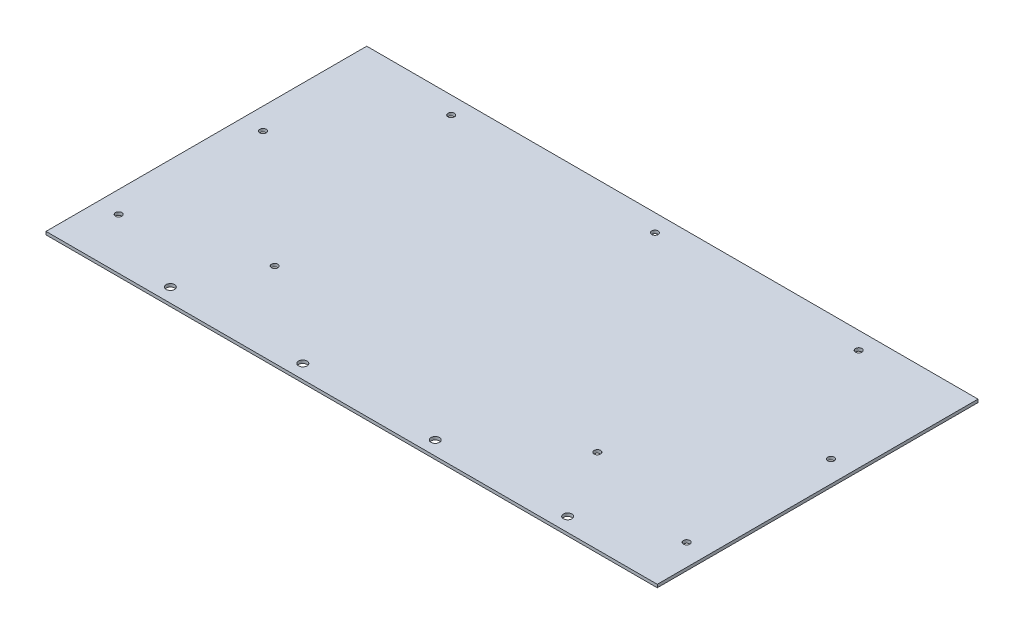
SolidWorks part; units mm, degrees
material "6061-T6 (SS)"
ref_plane "X-Y Datum" through (0, 0, 0) normal (0, 0, 1) x (1, 0, 0)
ref_plane "X-Z Datum" through (0, 0, 0) normal (0, 1, 0) x (1, 0, 0)
ref_plane "Y-Z Datum" through (0, 0, 0) normal (1, 0, 0) x (0, 0, -1)
sketch "Sketch1" plane through (0, 0, 0) normal (0, 0, 1) x (1, 0, 0)
  line L1 (-228.6115, -1.143) -> (228.6115, -1.143)
  line L2 (-228.6115, -1.143) -> (-228.6115, 1.143)
  line L3 (-228.6115, 1.143) -> (228.6115, 1.143)
  line L4 (228.6115, -1.143) -> (228.6115, 1.143)
  line L5 (-228.6115, -1.143) -> (228.6115, 1.143) construction
  line L6 (-228.6115, 1.143) -> (228.6115, -1.143) construction
  point P0 (0, 0)
  dimension "D1" = 2.286
  dimension "D2" = 457.223
extrude "Boss-Extrude1" add sketch "Sketch1" along normal blind 238.3152
sketch "Sketch2" plane through (0, 0, 0) normal (0, 0, -1) x (-1, 0, 0)
  line L22 (-228.6115, 1.143) -> (-228.6115, -1.143)
  line L23 (-228.6115, -1.143) -> (228.6115, -1.143)
  line L24 (228.6115, -1.143) -> (228.6115, 1.143)
  line L25 (228.6115, 1.143) -> (-228.6115, 1.143)
  line L26 (-228.6115, 1.143) -> (-228.6115, -1.143)
  line L27 (-228.6115, -1.143) -> (228.6115, -1.143)
  line L28 (228.6115, -1.143) -> (228.6115, 1.143)
  line L29 (228.6115, 1.143) -> (-228.6115, 1.143)
  dimension "D1" = 0
extrude "Boss-Extrude2" [suppressed] add sketch "Sketch2" along normal blind 3.175
sketch "Sketch9" plane through (0, 1.143, 0) normal (0, 1, 0) x (1, 0, 0)
  line L0 (-146.0615, -238.3152) -> (-146.0615, -229.4252) construction
  line L1 (228.6115, -238.3152) -> (-228.6115, -238.3152) construction
  line L2 (-228.6115, -238.3152) -> (-228.6115, 0) construction
  circle A0 centre (-146.0615, -229.4252) radius 3.175
  dimension "D2" = 82.55
  dimension "D3" = 6.35
  dimension "D1" = 8.89
extrude "Cut-Extrude10" cut sketch "Sketch9" against normal blind 2.54
pattern_linear "LPattern1" count 4 spacing 99.06 along (1, 0, 0) of "Cut-Extrude10"
sketch "Sketch10" plane through (0, -1.143, 0) normal (0, -1, 0) x (1, 0, 0)
  circle A0 centre (151.1185, 229.4252) radius 3.175 construction
  circle A1 centre (52.0585, 229.4252) radius 3.175 construction
  circle A2 centre (-47.0015, 229.4252) radius 3.175 construction
  circle A3 centre (-146.0615, 229.4252) radius 3.175 construction
  circle A4 centre (151.1185, 229.4252) radius 3.175
  circle A5 centre (52.0585, 229.4252) radius 3.175
  circle A6 centre (-47.0015, 229.4252) radius 3.175
  circle A7 centre (-146.0615, 229.4252) radius 3.175
sketch "Sketch15" plane through (0, 0, 238.3152) normal (0, 0, 1) x (1, 0, 0)
  line L4 (228.6115, -1.143) -> (228.6115, 1.143)
  line L5 (228.6115, 1.143) -> (-228.6115, 1.143)
  line L6 (-228.6115, 1.143) -> (-228.6115, -1.143)
  line L7 (-228.6115, -1.143) -> (228.6115, -1.143)
  line L8 (228.6115, -1.143) -> (228.6115, 1.143)
  line L9 (228.6115, 1.143) -> (-228.6115, 1.143)
  line L10 (-228.6115, 1.143) -> (-228.6115, -1.143)
  line L11 (-228.6115, -1.143) -> (228.6115, -1.143)
  dimension "D1" = 0
extrude "Boss-Extrude3" add sketch "Sketch15" along normal blind 1.5875
sketch "Sketch17" plane through (0, -1.143, 0) normal (0, -1, 0) x (1, 0, 0)
  point P0 (-212.419, 201.7248)
  point P1 (-212.419, 93.7748)
  point P3 (-152.4, 13.0175)
  point P5 (0, 13.0175)
  point P7 (152.4, 13.0175)
  point P9 (212.419, 93.7748)
  point P11 (212.419, 201.7248)
  point P13 (120.65, 176.776)
  point P15 (-120.65, 176.776)
hole_wizard "M4 Clearance Hole1" positions "Sketch17" profile "Sketch18" hole size "M4" standard "ANSI Metric" end condition through all
sketch "Sketch18" plane through (-212.419, -1.143, 201.7248) normal (1, 0, 0) x (0, 0, -1)
  line L0 (0, 0) -> (0, 2.286)
  line L1 (0, 2.286) -> (2.4, 2.286)
  line L2 (2.4, 2.286) -> (2.4, 0)
  line L5 (2.4, 0) -> (0, 0)
  line L11 (0, -6.35) -> (0, 107.95) construction
  dimension "Thru Hole Dia." = 4.8
  dimension "Thru Hole Depth" = 2.286
